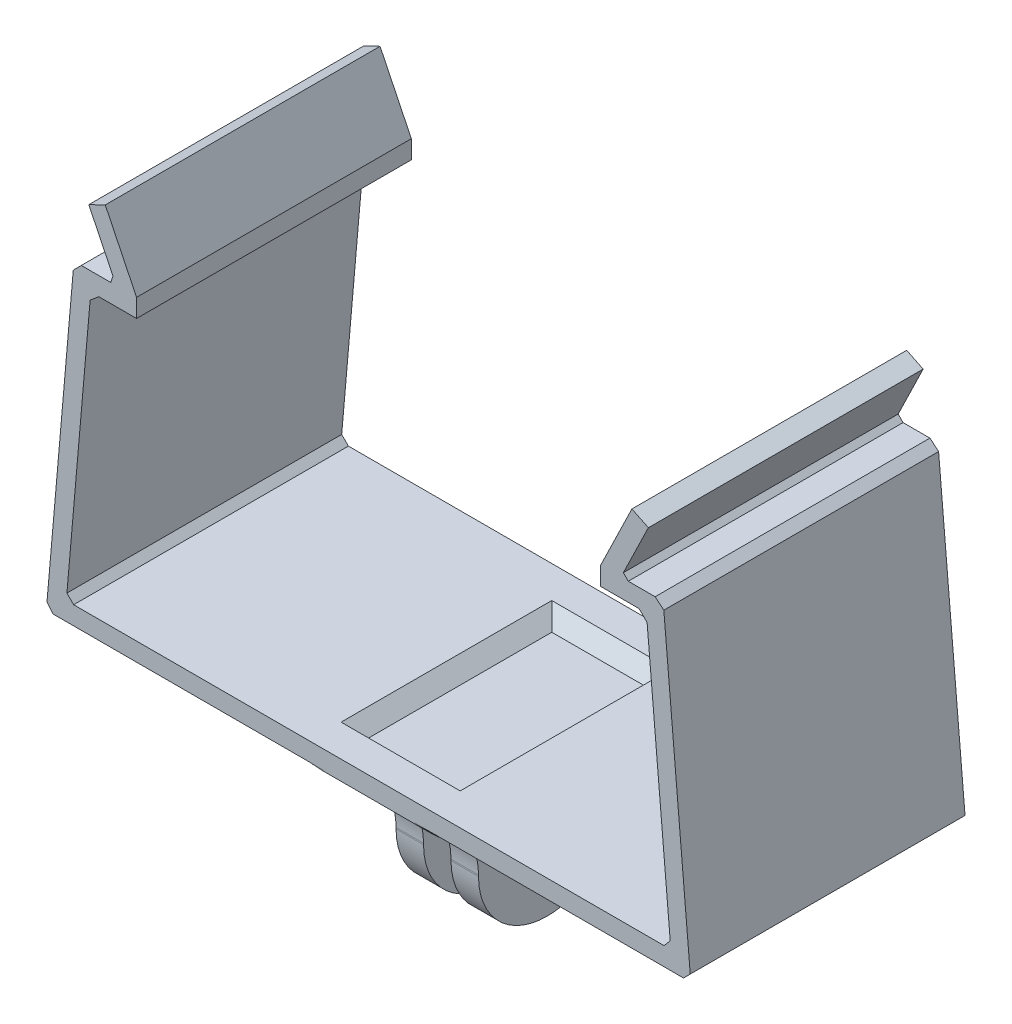
SolidWorks part; units mm, degrees
ref_plane "Front Plane" through (0, 0, 0) normal (0, 0, 1) x (1, 0, 0)
ref_plane "Top Plane" through (0, 0, 0) normal (0, 1, 0) x (1, 0, 0)
ref_plane "Right Plane" through (0, 0, 0) normal (1, 0, 0) x (0, 0, -1)
sketch "Sketch1" plane through (0, 0, 0) normal (0, 0, 1) x (1, 0, 0)
  line L0 (0, 0) -> (0, 24) construction
  line L1 (-32.1643, 32.5) -> (-27.5552, 32.5)
  line L2 (-30.3316, 30.5) -> (-33, 0)
  line L3 (-33, 0) -> (0, 0)
  line L4 (-32.1643, 32.5) -> (-35.1826, -2)
  line L5 (-35.1826, -2) -> (0, -2)
  line L6 (-30.3316, 30.5) -> (-25.3316, 30.5)
  line L7 (-25.3316, 32.5) -> (-25.3316, 30.5)
  line L8 (35.1826, -2) -> (0, -2)
  line L9 (33, 0) -> (0, 0)
  line L10 (25.3316, 32.5) -> (25.3316, 30.5)
  line L11 (30.3316, 30.5) -> (25.3316, 30.5)
  line L12 (32.1643, 32.5) -> (35.1826, -2)
  line L13 (30.3316, 30.5) -> (33, 0)
  line L14 (32.1643, 32.5) -> (27.5552, 32.5)
  line L15 (-25.3316, 32.5) -> (-28.7479, 39.5303)
  line L16 (-27.5552, 32.5) -> (-30.5468, 38.6562)
  line L17 (-28.7479, 39.5303) -> (-30.5468, 38.6562)
  line L18 (-27.1305, 31.6259) -> (-30.5468, 38.6562) construction
  line L19 (-32.1643, 32.5) -> (-25.3316, 32.5) construction
  line L20 (28.7479, 39.5303) -> (30.5468, 38.6562)
  line L21 (27.5552, 32.5) -> (30.5468, 38.6562)
  line L22 (25.3316, 32.5) -> (28.7479, 39.5303)
  dimension "D1" = 85
  dimension "D2" = 30.5
  dimension "D3" = 33
  dimension "D4" = 2
  dimension "D5" = 5
  dimension "D6" = 2
extrude "Boss-Extrude1" add sketch "Sketch1" along normal blind 30
sketch "Sketch5" plane through (0, -2, 0) normal (0, -1, 0) x (1, 0, 0)
  line L0 (-15, 0) -> (-15, 30)
  line L3 (-15, 30) -> (15, 30)
  line L4 (-15, 0) -> (15, 0)
  line L5 (0, 0) -> (0, 50) construction
  line L6 (-35.1826, 30) -> (35.1826, 30) construction
  line L7 (15, 0) -> (15, 30)
  dimension "D1" = 30
extrude "Boss-Extrude2" add sketch "Sketch5" along normal blind 1.6
sketch "Sketch9" plane through (0, 0, 0) normal (0, 1, 0) x (1, 0, 0)
  line L1 (-5, -25) -> (-5, -5)
  line L2 (-5, -25) -> (5, -25)
  line L3 (5, -25) -> (5, -5)
  line L4 (-5, -5) -> (5, -5)
  line L5 (-5, -25) -> (5, -5) construction
  line L6 (5, -25) -> (-5, -5) construction
  point P0 (0, -15)
  dimension "D1" = 10
  dimension "D3" = 20
extrude "Cut-Extrude4" cut sketch "Sketch9" against normal blind 1.5
chamfer "Chamfer4" distance 1.5 angle 45 4 edges at (0, 0, 25) (-5, 0, 15) (0, 0, 5) (5, 0, 15)
fillet "Fillet13" radius 10 4 edges at (-15, -2.8, 0) (15, -2.8, 0) (15, -2.8, 30) (-15, -2.8, 30)
chamfer "Chamfer5" distance 1.5 angle 45 8 edges at (15, -3.6, 15) (12.0711, -3.6, 27.0711) (12.0711, -3.6, 2.9289) (0, -3.6, 30) (0, -3.6, 0) (-12.0711, -3.6, 27.0711) (-12.0711, -3.6, 2.9289) (-15, -3.6, 15)
chamfer "Chamfer6" distance 0.8 angle 45 4 edges at (-35.1826, -2, 15) (35.1826, -2, 15) (33, 0, 15) (-33, 0, 15)
chamfer "Chamfer7" distance 0.8 angle 45 6 edges at (-30.3316, 30.5, 15) (30.3316, 30.5, 15) (32.1643, 32.5, 15) (-32.1643, 32.5, 15) (27.5552, 32.5, 15) (-27.5552, 32.5, 15)
sketch "Sketch10" plane through (0, -3.6, 0) normal (0, -1, 0) x (1, 0, 0)
  line L1 (-4.5, 7.5) -> (4.5, 7.5)
  line L2 (-4.5, 7.5) -> (-4.5, 22.5)
  line L3 (-4.5, 22.5) -> (4.5, 22.5)
  line L4 (4.5, 7.5) -> (4.5, 22.5)
  line L5 (-4.5, 7.5) -> (4.5, 22.5) construction
  line L6 (-4.5, 22.5) -> (4.5, 7.5) construction
  point P0 (0, 15)
  dimension "D1" = 9
  dimension "D2" = 15
extrude "Boss-Extrude3" add sketch "Sketch10" along normal blind 15
fillet "Fillet14" radius 7.5 4 edges at (0, -3.6, 7.5) (0, -3.6, 22.5) (0, -18.6, 7.5) (0, -18.6, 22.5)
hole_wizard "Ø5.2 (5.2) Diameter Hole1" positions "Sketch11" profile "Sketch12" hole size "Ø5.2" standard "ANSI Metric" end condition through all
sketch "Sketch11" plane through (-4.5, 0, 0) normal (-1, 0, 0) x (0, 0, 1)
  point P0 (15, -11.1)
sketch "Sketch12" plane through (-4.5, -11.1, 15) normal (0, 1, 0) x (0, 0, 1)
  line L0 (0, 0) -> (0, 39.6183)
  line L1 (0, 39.6183) -> (2.6, 39.6183)
  line L2 (2.6, 39.6183) -> (2.6, 0)
  line L5 (2.6, 0) -> (0, 0)
  line L11 (0, -6.35) -> (0, 107.95) construction
  dimension "Thru Hole Dia." = 5.2
  dimension "Thru Hole Depth" = 39.6183
sketch "Sketch13" plane through (0, -3.6, 0) normal (0, -1, 0) x (1, 0, 0)
  line L0 (4.5, 15) -> (-4.5, 15) construction
  line L1 (-1.5, 28.5) -> (1.5, 28.5)
  line L2 (-1.5, 28.5) -> (-1.5, 1.5)
  line L3 (-1.5, 1.5) -> (1.5, 1.5)
  line L4 (1.5, 28.5) -> (1.5, 1.5)
  line L5 (-1.5, 28.5) -> (1.5, 1.5) construction
  line L6 (-1.5, 1.5) -> (1.5, 28.5) construction
  line L7 (-4.5, 1.5) -> (4.5, 1.5) construction
  point P0 (0, 15)
  dimension "D1" = 3
extrude "Cut-Extrude5" cut sketch "Sketch13" along normal blind 15
chamfer "Chamfer8" distance 1.5 angle 45 2 edges at (4.5, -3.6, 15) (-4.5, -3.6, 15)
